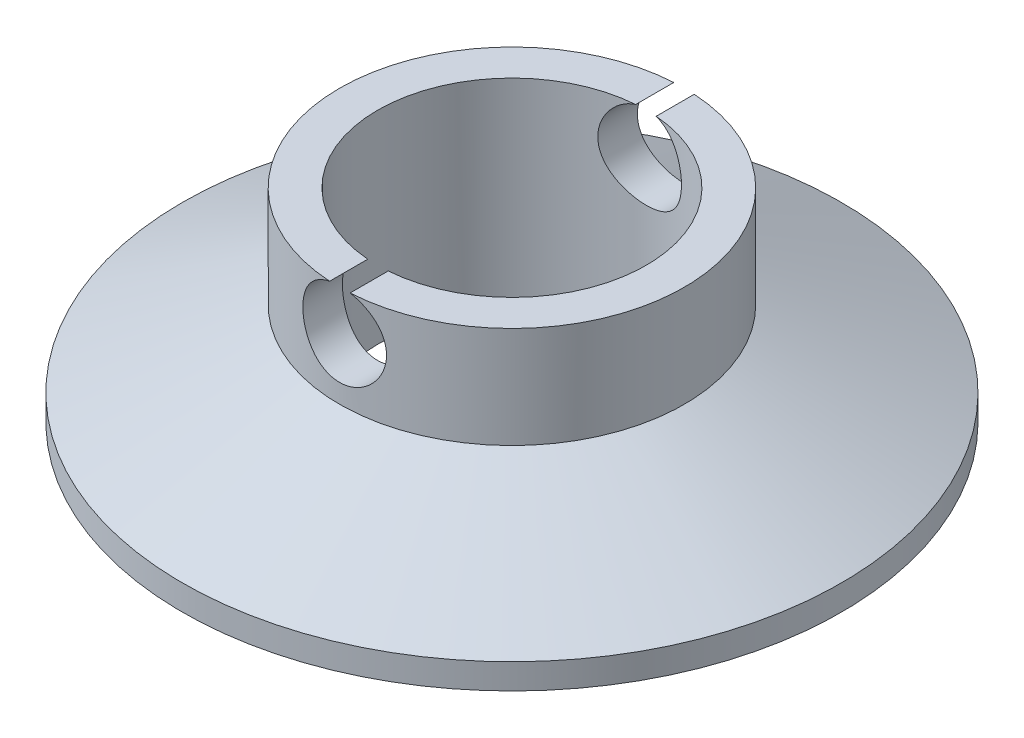
SolidWorks part; units mm, degrees
ref_plane "前视基准面" through (0, 0, 0) normal (0, 0, 1) x (1, 0, 0)
ref_plane "上视基准面" through (0, 0, 0) normal (0, 1, 0) x (1, 0, 0)
ref_plane "右视基准面" through (0, 0, 0) normal (1, 0, 0) x (0, 0, -1)
sketch "草图1" plane through (0, 0, 0) normal (0, 0, 1) x (1, 0, 0)
  line L0 (0, 0) -> (-7.7, 0)
  line L1 (-7.7, 0) -> (-7.7, 1)
  line L2 (-7.7, 1) -> (-1.5, 4)
  line L3 (-1.5, 4) -> (-1.5, 8)
  line L4 (-1.5, 8) -> (0, 8)
  line L5 (0, 8) -> (0, 0)
  line L6 (5.3, 12.9892) -> (5.3, -5.2583) construction
  dimension "D1" = 13
  dimension "D2" = 4
  dimension "D3" = 8
  dimension "D4" = 5.3
  dimension "D5" = 1.5
  dimension "D6" = 1
revolve "旋转1" add sketch "草图1" angle 360 about L6
ref_axis "基准轴1" through (5.3, 0, 0) along (0, 1, 0)
sketch "草图2" plane through (0, 0, 0) normal (0, 0, 1) x (1, 0, 0)
  line L0 (5.3, 0) -> (5.3, 8) construction
  line L2 (12.1, 8) -> (-1.5, 8) construction
  circle A0 centre (5.3, 6.4) radius 1.65
  dimension "D1" = 3.3
  dimension "D2" = 1.6
extrude "切除-拉伸3" cut sketch "草图2" against normal blind 10 and the other way blind 10
